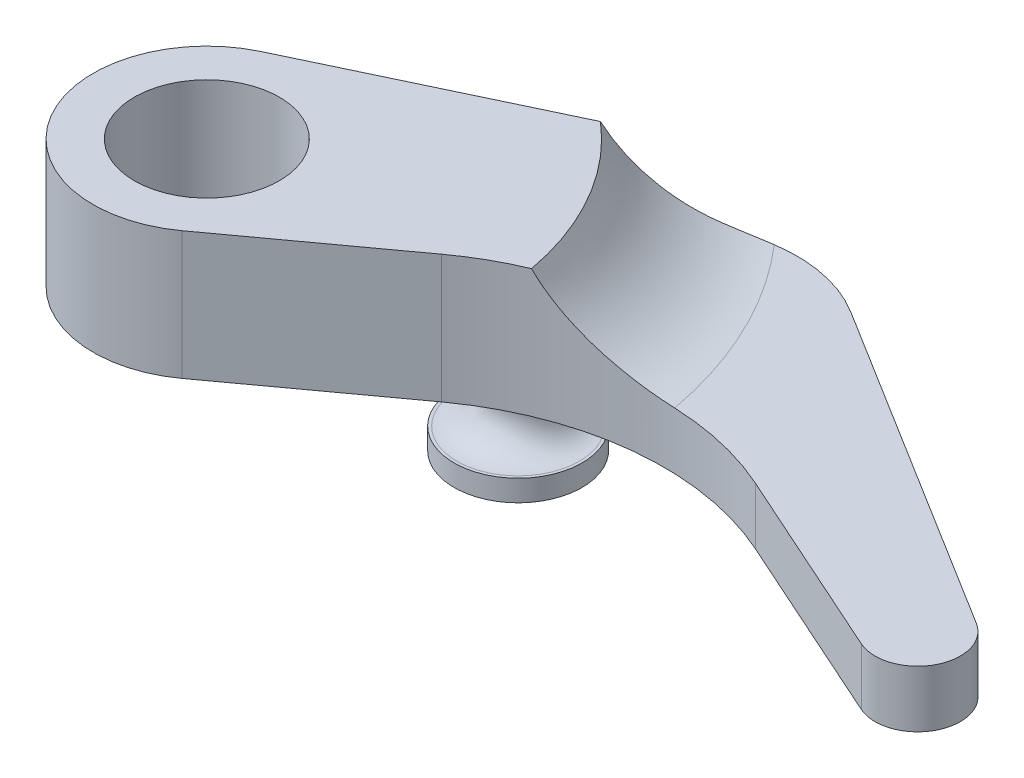
SolidWorks part; units mm, degrees
ref_plane "Front Plane" through (0, 0, 0) normal (0, 0, 1) x (1, 0, 0)
ref_plane "Top Plane" through (0, 0, 0) normal (0, 1, 0) x (1, 0, 0)
ref_plane "Right Plane" through (0, 0, 0) normal (1, 0, 0) x (0, 0, -1)
sketch "Sketch1" plane through (0, 0, 0) normal (0, 1, 0) x (1, 0, 0)
  line L0 (0, 0) -> (0, 20) construction
  line L1 (0, 0) -> (50, 0) construction
  line L9 (-3.4241, 7.2302) -> (23.5403, 20)
  line L10 (23.5403, 20) -> (51.5851, 2.5471)
  line L11 (4.7128, -6.4645) -> (24.6604, 8.0781)
  line L12 (24.6604, 8.0781) -> (48.7722, -2.7372)
  circle A0 centre (0, 0) radius 5.1
  arc A2 (-3.4241, 7.2302) -> (4.7128, -6.4645) centre (0, 0) ccw
  arc A8 (48.7722, -2.7372) -> (51.5851, 2.5471) centre (50, 0) ccw
  dimension "D1" = 10.2
  dimension "D2" = 6
  dimension "D3" = 8
  dimension "D4" = 20
  dimension "D5" = 50
extrude "Boss-Extrude1" add sketch "Sketch1" along normal blind 9
sketch "Sketch3" plane through (0, 9, 0) normal (0, 1, 0) x (1, 0, 0)
  line L1 (69.061, 26.8013) -> (4.6381, 26.8013)
  line L2 (69.061, 26.8013) -> (69.061, -8.6199)
  line L3 (69.061, -8.6199) -> (17.6419, -8.6199)
  line L4 (4.6381, 26.8013) -> (4.6381, 19.0795)
  arc A0 (17.6419, -8.6199) -> (4.6381, 19.0795) centre (0, 0) ccw
extrude "Cut-Extrude1" cut sketch "Sketch3" against normal blind 5
fillet "Fillet2" radius 20 1 edges at (24.6604, 2, -8.0781)
fillet "Fillet3" radius 10 1 edges at (23.5403, 2, -20)
fillet "Fillet1" radius 10 1 edges at (17.0295, 4, -9.7742)
ref_plane "Plane1" through (0, 2, 0) normal (0, -1, 0) x (-1, 0, 0)
sketch "Sketch4" plane through (0, 2, 0) normal (0, -1, 0) x (-1, 0, 0)
  line L4 (-32.9987, -1.69) -> (-46.5213, -7.7555)
  line L5 (-7.9529, -10.9088) -> (-18.5224, -3.2032)
  line L6 (-32.9987, -1.69) -> (-46.5213, -7.7555)
  line L7 (-7.9529, -10.9088) -> (-18.5224, -3.2032)
  arc A2 (-18.5224, -3.2032) -> (-32.9987, -1.69) centre (-27.0644, -14.92) ccw
  arc A3 (-18.5224, -3.2032) -> (-32.9987, -1.69) centre (-27.0644, -14.92) ccw
  dimension "D1" = 5.5
sketch "Sketch5" plane through (0, 0, 0) normal (0, -1, 0) x (1, 0, 0)
  circle A0 centre (14.4329, -7.4591) radius 2
  point P2 (22.9315, -11.9588)
  point P3 (14.4329, -7.4591)
  dimension "D1" = 4
extrude "Boss-Extrude2" add sketch "Sketch5" along normal blind 5
sketch "Sketch6" plane through (0, -5, 0) normal (0, -1, 0) x (1, 0, 0)
  circle A0 centre (14.4329, -7.4591) radius 4.5
  dimension "D1" = 9
extrude "Boss-Extrude3" add sketch "Sketch6" along normal blind 1.5
fillet "Fillet4" radius 2.3 2 edges at (14.4329, 0, -5.4591) (14.4329, -5, -9.4591)
